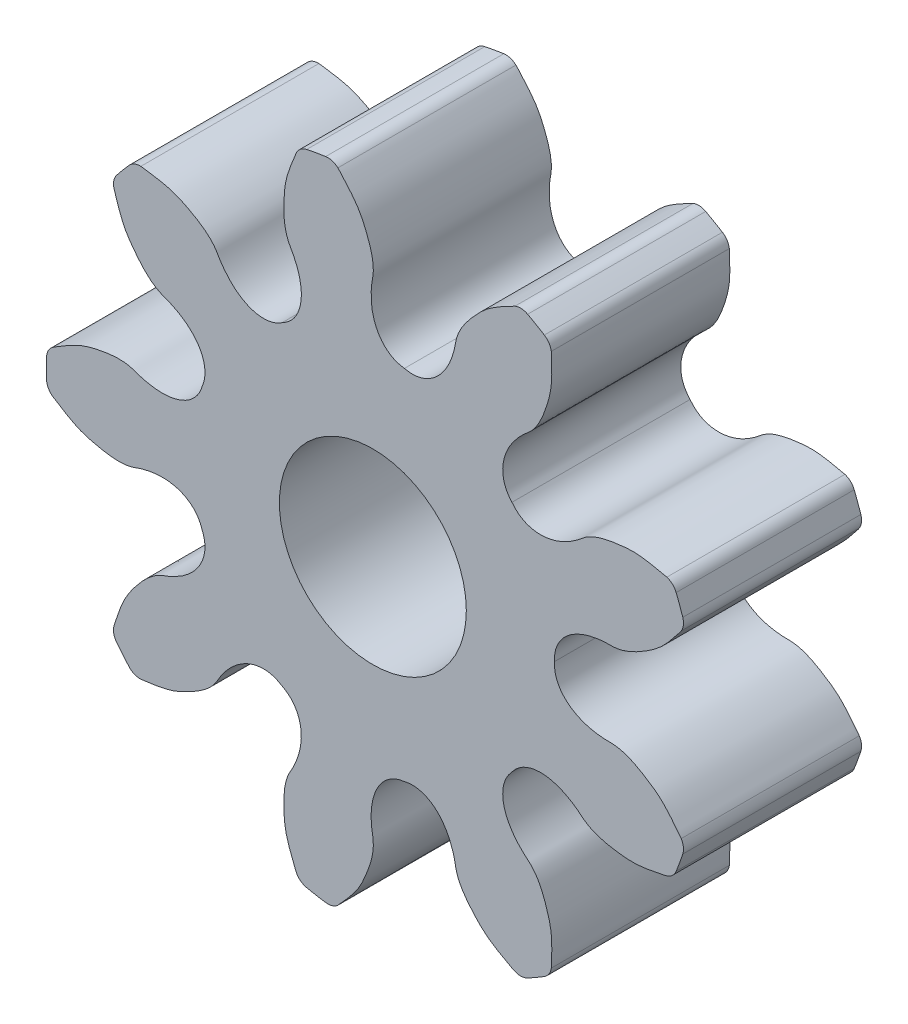
SolidWorks part; units mm, degrees
ref_plane "Front Plane" through (0, 0, 0) normal (0, 0, 1) x (1, 0, 0)
ref_plane "Top Plane" through (0, 0, 0) normal (0, 1, 0) x (1, 0, 0)
ref_plane "Right Plane" through (0, 0, 0) normal (1, 0, 0) x (0, 0, -1)
ref_axis "Axis1" through (0, 0, 55) along (0, 0, -1)
sketch "SketchRevolveSpurPinion" plane through (0, 0, 0) normal (1, 0, 0) x (0, 0, -1)
  line L0 (0, 0) -> (1, 0) construction
  line L1 (-3, 0) -> (-3, 11)
  line L2 (-3, 11) -> (3, 11)
  line L3 (3, 11) -> (3, 0)
  line L4 (3, 0) -> (-3, 0)
  dimension "Side1" = 3
  dimension "OutsideRadius" = 11
  dimension "Side2" = 3
revolve "SpurPinion" add sketch "SketchRevolveSpurPinion" angle 360 about L0
sketch "SketchToothSpurPinion" plane through (0, 0, 0) normal (0, 0, 1) x (1, 0, 0)
  line L0 (6.1204, 0) -> (11.1, 0) construction
  arc A0 (10.5353, 3.5168) -> (10.5353, -3.5168) centre (0, 0) cw
  spline S0 degree 3 poles (6.1204, 0) (6.1204, 0.0249) (6.1197, 0.0583) (6.1201, 0.1068) (6.1213, 0.1454) (6.1248, 0.1905) (6.1301, 0.2353) (6.1373, 0.2797) (6.1464, 0.3236) (6.1572, 0.367) (6.1698, 0.4098) (6.1841, 0.4518) (6.1999, 0.4931) (6.2173, 0.5336) (6.2362, 0.5732) (6.2565, 0.6119) (6.2782, 0.6497) (6.3011, 0.6865) (6.3253, 0.7223) (6.3506, 0.7572) (6.377, 0.7911) (6.4045, 0.824) (6.4331, 0.8559) (6.4625, 0.8868) (6.4929, 0.9167) (6.5242, 0.9457) (6.5564, 0.9738) (6.5893, 1.0009) (6.6231, 1.027) (6.6576, 1.0523) (6.6929, 1.0766) (6.7289, 1.1) (6.7656, 1.1226) (6.803, 1.1443) (6.8411, 1.1651) (6.8798, 1.1851) (6.9192, 1.2043) (6.9592, 1.2226) (6.9999, 1.24) (7.0412, 1.2567) (7.0831, 1.2725) (7.1256, 1.2876) (7.1686, 1.3018) (7.2123, 1.3152) (7.2566, 1.3278) (7.3015, 1.3396) (7.3469, 1.3506) (7.3929, 1.3609) (7.4394, 1.3703) (7.4866, 1.3789) (7.5342, 1.3867) (7.5824, 1.3937) (7.6312, 1.3999) (7.6805, 1.4053) (7.7303, 1.4099) (7.7806, 1.4136) (7.8315, 1.4166) (7.8828, 1.4187) (7.9347, 1.4199) (7.9871, 1.4206) (8.2425, 1.4155) (8.6415, 1.5295) (9.2102, 1.8465) (9.6404, 2.1372) (9.9325, 2.4592) (10.0979, 2.6478) (10.3211, 2.9481) (10.4981, 3.1225) (10.5353, 3.5168) knots 0.50263 0.50263 0.50263 0.50263 0.508845 0.51095 0.514711 0.518467 0.522214 0.525952 0.52968 0.533395 0.537097 0.540785 0.544459 0.548118 0.551762 0.555391 0.559007 0.56261 0.5662 0.569779 0.573348 0.576908 0.580462 0.58401 0.587554 0.591097 0.594639 0.598183 0.60173 0.605282 0.608842 0.61241 0.615989 0.61958 0.623184 0.626805 0.630442 0.634098 0.637774 0.641471 0.645191 0.648935 0.652705 0.656501 0.660325 0.664178 0.66806 0.671974 0.67592 0.679898 0.68391 0.687957 0.692039 0.696157 0.700313 0.704506 0.708737 0.713008 0.717318 0.721668 0.726059 0.780966 0.821469 0.888945 0.908617 0.929559 0.95177 1 1 1 1
  spline S1 degree 3 poles (6.1204, 0) (6.1204, -0.0249) (6.1197, -0.0583) (6.1201, -0.1068) (6.1213, -0.1454) (6.1248, -0.1905) (6.1301, -0.2353) (6.1373, -0.2797) (6.1464, -0.3236) (6.1572, -0.367) (6.1698, -0.4098) (6.1841, -0.4518) (6.1999, -0.4931) (6.2173, -0.5336) (6.2362, -0.5732) (6.2565, -0.6119) (6.2782, -0.6497) (6.3011, -0.6865) (6.3253, -0.7223) (6.3506, -0.7572) (6.377, -0.7911) (6.4045, -0.824) (6.4331, -0.8559) (6.4625, -0.8868) (6.4929, -0.9167) (6.5242, -0.9457) (6.5564, -0.9738) (6.5893, -1.0009) (6.6231, -1.027) (6.6576, -1.0523) (6.6929, -1.0766) (6.7289, -1.1) (6.7656, -1.1226) (6.803, -1.1443) (6.8411, -1.1651) (6.8798, -1.1851) (6.9192, -1.2043) (6.9592, -1.2226) (6.9999, -1.24) (7.0412, -1.2567) (7.0831, -1.2725) (7.1256, -1.2876) (7.1686, -1.3018) (7.2123, -1.3152) (7.2566, -1.3278) (7.3015, -1.3396) (7.3469, -1.3506) (7.3929, -1.3609) (7.4394, -1.3703) (7.4866, -1.3789) (7.5342, -1.3867) (7.5824, -1.3937) (7.6312, -1.3999) (7.6805, -1.4053) (7.7303, -1.4099) (7.7806, -1.4136) (7.8315, -1.4166) (7.8828, -1.4187) (7.9347, -1.4199) (7.9871, -1.4206) (8.2425, -1.4155) (8.6415, -1.5295) (9.2102, -1.8465) (9.6404, -2.1372) (9.9325, -2.4592) (10.0979, -2.6478) (10.3211, -2.9481) (10.4981, -3.1225) (10.5353, -3.5168) knots 0.50263 0.50263 0.50263 0.50263 0.508845 0.51095 0.514711 0.518467 0.522214 0.525952 0.52968 0.533395 0.537097 0.540785 0.544459 0.548118 0.551762 0.555391 0.559007 0.56261 0.5662 0.569779 0.573348 0.576908 0.580462 0.58401 0.587554 0.591097 0.594639 0.598183 0.60173 0.605282 0.608842 0.61241 0.615989 0.61958 0.623184 0.626805 0.630442 0.634098 0.637774 0.641471 0.645191 0.648935 0.652705 0.656501 0.660325 0.664178 0.66806 0.671974 0.67592 0.679898 0.68391 0.687957 0.692039 0.696157 0.700313 0.704506 0.708737 0.713008 0.717318 0.721668 0.726059 0.780966 0.821469 0.888945 0.908617 0.929559 0.95177 1 1 1 1
  point P67 (10.5353, 3.5168)
extrude "ToothExtrudeCutSpurPinion" cut sketch "SketchToothSpurPinion" against normal blind 3 and the other way blind 3
pattern_circular "PatternSpurPinion" count 9 every 40 about axis through (0, 0, 55) along (0, 0, -1) of "ToothExtrudeCutSpurPinion"
sketch "BoreRevolveSketch" plane through (0, 0, 0) normal (1, 0, 0) x (0, 0, -1)
  line L0 (0, 0) -> (1, 0) construction
  line L1 (-3, 0) -> (3, 0)
  line L2 (3, 0) -> (3, 3.15)
  line L3 (3, 3.15) -> (-3, 3.15)
  line L4 (-3, 3.15) -> (-3, 0)
  dimension "BoreSide1" = 3
  dimension "TaperSide1" = 3.15
  dimension "BoreSide2" = 3
  dimension "TaperSide2" = 3.15
revolve "BoreRevolveCut" cut sketch "BoreRevolveSketch" angle 360 about L0
sketch "AuxiliarySketchSpurPinion" plane through (0, 0, 0) normal (0, 0, 1) x (1, 0, 0)
  circle A0 centre (0, 0) radius 9 construction
  circle A1 centre (0, 0) radius 8.4572 construction
  circle A2 centre (0, 0) radius 9.446 construction
  circle A3 centre (0, 0) radius 11 construction
  circle A4 centre (0, 0) radius 6.1204 construction
  dimension "PitchDiameter" = 18
  dimension "BaseDiameter" = 16.9145
  dimension "FormDiameter" = 18.8921
  dimension "MajorDiameter" = 22
  dimension "MinorDiameter" = 12.2407
fillet "Fillet1" radius 0.5 10 edges at (10.4977, -3.286, 0) (10.4977, 3.286, 0) (10.1539, 4.2306, 0) (5.9295, 9.2651, 0) (5.059, 9.7676, 0) (-10.9885, 0.5026, 0) (-8.7407, 6.6783, 0) (-8.0947, 7.4483, 0) (-2.4031, 10.7343, 0) (-1.4132, 10.9089, 0)
fillet "Fillet2" radius 0.5 8 edges at (10.1539, -4.2306, 0) (5.9295, -9.2651, 0) (5.059, -9.7676, 0) (-1.4132, -10.9089, 0) (-2.4031, -10.7343, 0) (-8.0947, -7.4483, 0) (-8.7407, -6.6783, 0) (-10.9885, -0.5026, 0)
